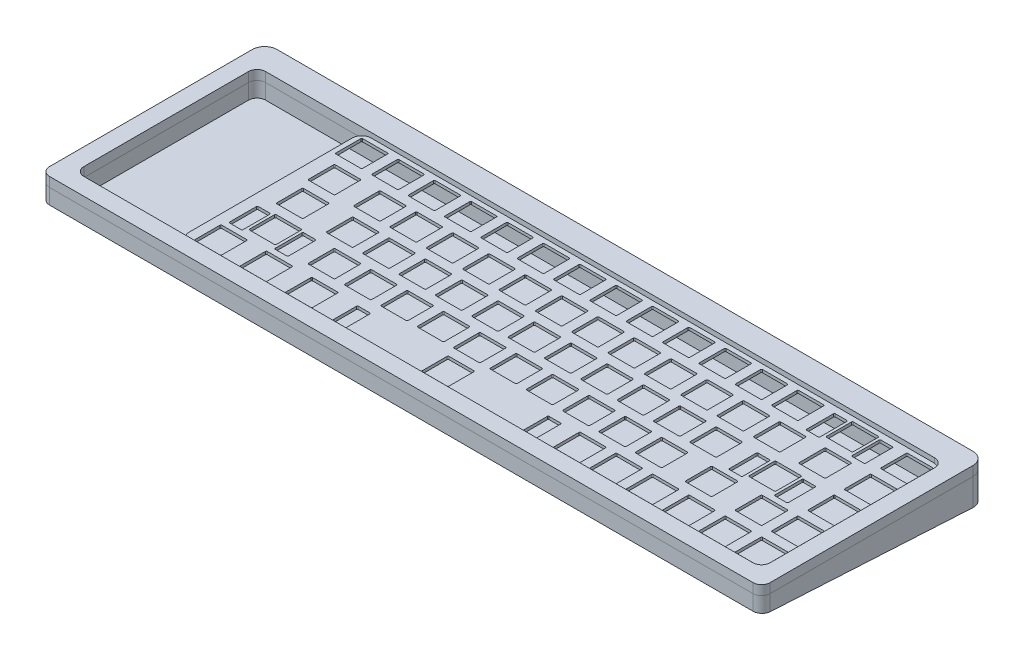
SolidWorks part; units mm, degrees
ref_plane "Front Plane" through (0, 0, 0) normal (0, 0, 1) x (1, 0, 0)
ref_plane "Top Plane" through (0, 0, 0) normal (0, 1, 0) x (1, 0, 0)
ref_plane "Right Plane" through (0, 0, 0) normal (1, 0, 0) x (0, 0, -1)
sketch "Sketch1" plane through (0, 0, 0) normal (0, 1, 0) x (1, 0, 0)
  line L0 (-179.825, 47.6224) -> (-179.825, 47.625)
  line L1 (-179.8217, 47.625) -> (179.825, 47.625)
  line L2 (-179.825, 47.6224) -> (-179.825, -47.625)
  line L3 (-179.825, -47.625) -> (179.825, -47.625)
  line L4 (179.825, 47.625) -> (179.825, -47.625)
  line L5 (-179.825, 47.625) -> (179.825, -47.625) construction
  line L6 (-179.825, -47.625) -> (179.825, 47.625) construction
  line L7 (-179.825, 47.625) -> (-179.8217, 47.625)
  circle A4 centre (157.075, 19.175) radius 1.1
  circle A5 centre (136.925, -16.775) radius 1.1
  circle A6 centre (-153.475, 33.725) radius 1.1
  circle A7 centre (17.925, 22.275) radius 1.1
  circle A8 centre (17.875, -35.075) radius 1.1
  circle A9 centre (-130.375, -35.725) radius 1.1
  point P0 (0, 0)
  dimension "D4" = 2.2
  dimension "D7" = 2.2
  dimension "D8" = 2.2
  dimension "D9" = 2.2
  dimension "D10" = 2.2
  dimension "D11" = 2.2
  dimension "D1" = 359.65
  dimension "D2" = 95.25
  dimension "D5" = 22.75
  dimension "D6" = 28.45
  dimension "D12" = 42.9
  dimension "D13" = 30.85
  dimension "D14" = 25.35
  dimension "D15" = 161.9
  dimension "D16" = 12.55
  dimension "D17" = 161.95
  dimension "D18" = 11.9
  dimension "D19" = 49.45
  dimension "D20" = 13.9
  dimension "D21" = 26.35
sketch "Sketch2" plane through (0, 0, 0) normal (0, 1, 0) x (1, 0, 0)
  line L0 (-188.825, 54.625) -> (-188.825, 60.625)
  line L1 (-188.825, 60.625) -> (-182.825, 60.625)
  line L4 (-179.825, 46.625) -> (-179.825, -46.625)
  line L5 (-178.825, -47.625) -> (178.825, -47.625)
  line L6 (179.825, 46.625) -> (179.825, -46.625)
  line L7 (-178.825, 47.625) -> (178.825, 47.625)
  line L8 (-179.825, 46.625) -> (-179.825, 47.625)
  line L9 (-182.825, 60.625) -> (188.825, 60.625)
  line L10 (-188.825, 54.625) -> (-188.825, -56.625)
  line L11 (-188.825, -56.625) -> (188.825, -56.625)
  line L12 (188.825, 60.625) -> (188.825, -56.625)
  line L13 (-179.825, 47.625) -> (-178.825, 47.625)
  line L14 (-179.825, -46.625) -> (-179.825, -47.625)
  line L15 (-179.825, -47.625) -> (-178.825, -47.625)
  line L16 (178.825, -47.625) -> (179.825, -47.625)
  line L17 (179.825, -47.625) -> (179.825, -46.625)
  line L18 (178.825, 47.625) -> (179.825, 47.625)
  line L19 (179.825, 47.625) -> (179.825, 46.625)
  circle A0 centre (157.075, 19.175) radius 1.1 construction
  circle A1 centre (136.925, -16.775) radius 1.1 construction
  circle A2 centre (17.875, -35.075) radius 1.1 construction
  circle A3 centre (17.925, 22.275) radius 1.1 construction
  circle A4 centre (-153.475, 33.725) radius 1.1 construction
  circle A5 centre (-130.375, -35.725) radius 1.1 construction
  circle A10 centre (157.075, 19.175) radius 1.1
  circle A11 centre (136.925, -16.775) radius 1.1
  circle A12 centre (17.875, -35.075) radius 1.1
  circle A13 centre (17.925, 22.275) radius 1.1
  circle A14 centre (-153.475, 33.725) radius 1.1
  circle A15 centre (-130.375, -35.725) radius 1.1
  point P30 (0, 0)
  dimension "D1" = 13
  dimension "D2" = 9
  dimension "D3" = 9
  dimension "D4" = 9
extrude "Boss-Extrude1" add sketch "Sketch2" along normal blind 13
sketch "Sketch4" plane through (0, 0, 0) normal (0, -1, 0) x (1, 0, 0)
  line L1 (-188.825, -60.625) -> (188.825, -60.625) construction
  line L3 (-188.825, 56.625) -> (188.825, 56.625) construction
  line L4 (-179.825, 47.625) -> (-179.825, -47.625)
  line L5 (179.825, 47.625) -> (-179.825, 47.625)
  line L6 (179.825, -47.625) -> (179.825, 47.625)
  line L7 (-179.825, -47.625) -> (179.825, -47.625)
  line L8 (-179.825, 47.625) -> (-179.825, -47.625)
  line L10 (179.825, -47.625) -> (179.825, 47.625)
  line L11 (-179.825, -47.625) -> (179.825, -47.625)
  line L12 (188.825, -60.625) -> (188.825, 56.625)
  line L13 (-188.825, -60.625) -> (188.825, -60.625)
  line L14 (-188.825, -60.625) -> (-188.825, 56.625)
  line L15 (-188.825, 56.625) -> (188.825, 56.625)
  line M10 (-179.825, -47.625) -> (-179.825, 47.625)
  line M12 (-179.825, 47.625) -> (179.825, 47.625)
  line M14 (179.825, 47.625) -> (179.825, -47.625)
  line M16 (179.825, -47.625) -> (-179.825, -47.625)
  line M17 (-188.825, 56.625) -> (-188.825, -60.625)
  line M19 (-188.825, -60.625) -> (188.825, -60.625)
  line M21 (188.825, -60.625) -> (188.825, 56.625)
  line M23 (188.825, 56.625) -> (-188.825, 56.625)
  dimension "D1" = 0
extrude "Boss-Extrude3" add sketch "Sketch4" along normal blind 10.5 contours M17 M19 M21 M23 M16 M10 M12 M14 | M16 M14 M12 M10 region at (0, 0, 0) region at (0, 0, -56.6707)
sketch "Sketch12" plane through (-188.825, 0, 0) normal (-1, 0, 0) x (0, 0, 1)
  line L0 (-60.625, 0) -> (56.625, 0) construction
  line L1 (-60.625, 13) -> (-60.625, -10.5) construction
  line L2 (56.625, 13) -> (56.625, -10.5) construction
  line L3 (56.625, -10.5) -> (-60.625, -10.5) construction
  line L4 (-60.625, -10.5) -> (-60.625, -6.5)
  line L5 (-60.625, -6.5) -> (56.625, 0)
  line L6 (56.625, 0) -> (56.625, -10.5)
  line L7 (56.625, -10.5) -> (-60.625, -10.5)
  dimension "D1" = 10.5
  dimension "D2" = 4
extrude "Cut-Extrude3" cut sketch "Sketch12" against normal blind 400
sketch "Sketch9" plane through (0, 0, 0) normal (0, 1, 0) x (1, 0, 0)
  line L0 (-121.9453, 45.1) -> (-108.9453, 45.1)
  line L1 (-121.9453, 31.1) -> (-108.9453, 31.1)
  line L2 (-122.4453, 44.6) -> (-122.4453, 31.6)
  line L3 (-108.4453, 44.6) -> (-108.4453, 31.6)
  line L4 (-102.8953, 45.1) -> (-89.8953, 45.1)
  line L5 (-102.8953, 31.1) -> (-89.8953, 31.1)
  line L6 (-103.3953, 44.6) -> (-103.3953, 31.6)
  line L7 (-89.3953, 44.6) -> (-89.3953, 31.6)
  line L8 (-83.8453, 45.1) -> (-70.8453, 45.1)
  line L9 (-83.8453, 31.1) -> (-70.8453, 31.1)
  line L10 (-84.3453, 44.6) -> (-84.3453, 31.6)
  line L11 (-70.3453, 44.6) -> (-70.3453, 31.6)
  line L12 (-64.7953, 45.1) -> (-51.7953, 45.1)
  line L13 (-64.7953, 31.1) -> (-51.7953, 31.1)
  line L14 (-65.2953, 44.6) -> (-65.2953, 31.6)
  line L15 (-51.2953, 44.6) -> (-51.2953, 31.6)
  line L16 (-45.7453, 45.1) -> (-32.7453, 45.1)
  line L17 (-45.7453, 31.1) -> (-32.7453, 31.1)
  line L18 (-46.2453, 44.6) -> (-46.2453, 31.6)
  line L19 (-32.2453, 44.6) -> (-32.2453, 31.6)
  line L20 (-26.6953, 45.1) -> (-13.6953, 45.1)
  line L21 (-26.6953, 31.1) -> (-13.6953, 31.1)
  line L22 (-27.1953, 44.6) -> (-27.1953, 31.6)
  line L23 (-13.1953, 44.6) -> (-13.1953, 31.6)
  line L24 (-7.6453, 45.1) -> (5.3547, 45.1)
  line L25 (-7.6453, 31.1) -> (5.3547, 31.1)
  line L26 (-8.1453, 44.6) -> (-8.1453, 31.6)
  line L27 (5.8547, 44.6) -> (5.8547, 31.6)
  line L28 (11.4047, 45.1) -> (24.4047, 45.1)
  line L29 (11.4047, 31.1) -> (24.4047, 31.1)
  line L30 (10.9047, 44.6) -> (10.9047, 31.6)
  line L31 (24.9047, 44.6) -> (24.9047, 31.6)
  line L32 (30.4547, 45.1) -> (43.4547, 45.1)
  line L33 (30.4547, 31.1) -> (43.4547, 31.1)
  line L34 (29.9547, 44.6) -> (29.9547, 31.6)
  line L35 (43.9547, 44.6) -> (43.9547, 31.6)
  line L36 (49.5047, 45.1) -> (62.5047, 45.1)
  line L37 (49.5047, 31.1) -> (62.5047, 31.1)
  line L38 (49.0047, 44.6) -> (49.0047, 31.6)
  line L39 (63.0047, 44.6) -> (63.0047, 31.6)
  line L40 (68.5547, 45.1) -> (81.5547, 45.1)
  line L41 (68.5547, 31.1) -> (81.5547, 31.1)
  line L42 (68.0547, 44.6) -> (68.0547, 31.6)
  line L43 (82.0547, 44.6) -> (82.0547, 31.6)
  line L44 (87.6047, 45.1) -> (100.6047, 45.1)
  line L45 (87.6047, 31.1) -> (100.6047, 31.1)
  line L46 (87.1047, 44.6) -> (87.1047, 31.6)
  line L47 (101.1047, 44.6) -> (101.1047, 31.6)
  line L48 (106.6547, 45.1) -> (119.6547, 45.1)
  line L49 (106.6547, 31.1) -> (119.6547, 31.1)
  line L50 (106.1547, 44.6) -> (106.1547, 31.6)
  line L51 (120.1547, 44.6) -> (120.1547, 31.6)
  line L52 (135.2297, 45.1) -> (148.2297, 45.1)
  line L53 (135.2297, 31.1) -> (148.2297, 31.1)
  line L54 (134.7297, 44.6) -> (134.7297, 31.6)
  line L55 (148.7297, 44.6) -> (148.7297, 31.6)
  line L56 (150.6677, 44.1) -> (156.6677, 44.1)
  line L57 (150.6677, 29.1) -> (156.6677, 29.1)
  line L58 (150.1677, 43.6) -> (150.1677, 29.6)
  line L59 (157.1677, 43.6) -> (157.1677, 29.6)
  line L60 (126.7917, 44.1) -> (132.7917, 44.1)
  line L61 (126.7917, 29.1) -> (132.7917, 29.1)
  line L62 (126.2917, 43.6) -> (126.2917, 29.6)
  line L63 (133.2917, 43.6) -> (133.2917, 29.6)
  line L64 (163.8047, 45.1) -> (176.8047, 45.1)
  line L65 (163.8047, 31.1) -> (176.8047, 31.1)
  line L66 (163.3047, 44.6) -> (163.3047, 31.6)
  line L67 (177.3047, 44.6) -> (177.3047, 31.6)
  line L68 (-117.1828, 26.05) -> (-104.1828, 26.05)
  line L69 (-117.1828, 12.05) -> (-104.1828, 12.05)
  line L70 (-117.6828, 25.55) -> (-117.6828, 12.55)
  line L71 (-103.6828, 25.55) -> (-103.6828, 12.55)
  line L72 (-93.3703, 26.05) -> (-80.3703, 26.05)
  line L73 (-93.3703, 12.05) -> (-80.3703, 12.05)
  line L74 (-93.8703, 25.55) -> (-93.8703, 12.55)
  line L75 (-79.8703, 25.55) -> (-79.8703, 12.55)
  line L76 (-74.3203, 26.05) -> (-61.3203, 26.05)
  line L77 (-74.3203, 12.05) -> (-61.3203, 12.05)
  line L78 (-74.8203, 25.55) -> (-74.8203, 12.55)
  line L79 (-60.8203, 25.55) -> (-60.8203, 12.55)
  line L80 (-55.2703, 26.05) -> (-42.2703, 26.05)
  line L81 (-55.2703, 12.05) -> (-42.2703, 12.05)
  line L82 (-55.7703, 25.55) -> (-55.7703, 12.55)
  line L83 (-41.7703, 25.55) -> (-41.7703, 12.55)
  line L84 (-36.2203, 26.05) -> (-23.2203, 26.05)
  line L85 (-36.2203, 12.05) -> (-23.2203, 12.05)
  line L86 (-36.7203, 25.55) -> (-36.7203, 12.55)
  line L87 (-22.7203, 25.55) -> (-22.7203, 12.55)
  line L88 (-17.1703, 26.05) -> (-4.1703, 26.05)
  line L89 (-17.1703, 12.05) -> (-4.1703, 12.05)
  line L90 (-17.6703, 25.55) -> (-17.6703, 12.55)
  line L91 (-3.6703, 25.55) -> (-3.6703, 12.55)
  line L92 (1.8797, 26.05) -> (14.8797, 26.05)
  line L93 (1.8797, 12.05) -> (14.8797, 12.05)
  line L94 (1.3797, 25.55) -> (1.3797, 12.55)
  line L95 (15.3797, 25.55) -> (15.3797, 12.55)
  line L96 (20.9297, 26.05) -> (33.9297, 26.05)
  line L97 (20.9297, 12.05) -> (33.9297, 12.05)
  line L98 (20.4297, 25.55) -> (20.4297, 12.55)
  line L99 (34.4297, 25.55) -> (34.4297, 12.55)
  line L100 (39.9797, 26.05) -> (52.9797, 26.05)
  line L101 (39.9797, 12.05) -> (52.9797, 12.05)
  line L102 (39.4797, 25.55) -> (39.4797, 12.55)
  line L103 (53.4797, 25.55) -> (53.4797, 12.55)
  line L104 (59.0297, 26.05) -> (72.0297, 26.05)
  line L105 (59.0297, 12.05) -> (72.0297, 12.05)
  line L106 (58.5297, 25.55) -> (58.5297, 12.55)
  line L107 (72.5297, 25.55) -> (72.5297, 12.55)
  line L108 (78.0797, 26.05) -> (91.0797, 26.05)
  line L109 (78.0797, 12.05) -> (91.0797, 12.05)
  line L110 (77.5797, 25.55) -> (77.5797, 12.55)
  line L111 (91.5797, 25.55) -> (91.5797, 12.55)
  line L112 (97.1297, 26.05) -> (110.1297, 26.05)
  line L113 (97.1297, 12.05) -> (110.1297, 12.05)
  line L114 (96.6297, 25.55) -> (96.6297, 12.55)
  line L115 (110.6297, 25.55) -> (110.6297, 12.55)
  line L116 (116.1797, 26.05) -> (129.1797, 26.05)
  line L117 (116.1797, 12.05) -> (129.1797, 12.05)
  line L118 (115.6797, 25.55) -> (115.6797, 12.55)
  line L119 (129.6797, 25.55) -> (129.6797, 12.55)
  line L120 (139.9922, 26.05) -> (152.9922, 26.05)
  line L121 (139.9922, 12.05) -> (152.9922, 12.05)
  line L122 (139.4922, 25.55) -> (139.4922, 12.55)
  line L123 (153.4922, 25.55) -> (153.4922, 12.55)
  line L124 (163.8047, 26.05) -> (176.8047, 26.05)
  line L125 (163.8047, 12.05) -> (176.8047, 12.05)
  line L126 (163.3047, 25.55) -> (163.3047, 12.55)
  line L127 (177.3047, 25.55) -> (177.3047, 12.55)
  line L128 (-114.8016, 7) -> (-101.8016, 7)
  line L129 (-114.8016, -7) -> (-101.8016, -7)
  line L130 (-115.3016, 6.5) -> (-115.3016, -6.5)
  line L131 (-101.3016, 6.5) -> (-101.3016, -6.5)
  line L132 (-88.6078, 7) -> (-75.6078, 7)
  line L133 (-88.6078, -7) -> (-75.6078, -7)
  line L134 (-89.1078, 6.5) -> (-89.1078, -6.5)
  line L135 (-75.1078, 6.5) -> (-75.1078, -6.5)
  line L136 (-69.5578, 7) -> (-56.5578, 7)
  line L137 (-69.5578, -7) -> (-56.5578, -7)
  line L138 (-70.0578, 6.5) -> (-70.0578, -6.5)
  line L139 (-56.0578, 6.5) -> (-56.0578, -6.5)
  line L140 (-50.5078, 7) -> (-37.5078, 7)
  line L141 (-50.5078, -7) -> (-37.5078, -7)
  line L142 (-51.0078, 6.5) -> (-51.0078, -6.5)
  line L143 (-37.0078, 6.5) -> (-37.0078, -6.5)
  line L144 (-31.4578, 7) -> (-18.4578, 7)
  line L145 (-31.4578, -7) -> (-18.4578, -7)
  line L146 (-31.9578, 6.5) -> (-31.9578, -6.5)
  line L147 (-17.9578, 6.5) -> (-17.9578, -6.5)
  line L148 (-12.4078, 7) -> (0.5922, 7)
  line L149 (-12.4078, -7) -> (0.5922, -7)
  line L150 (-12.9078, 6.5) -> (-12.9078, -6.5)
  line L151 (1.0922, 6.5) -> (1.0922, -6.5)
  line L152 (6.6422, 7) -> (19.6422, 7)
  line L153 (6.6422, -7) -> (19.6422, -7)
  line L154 (6.1422, 6.5) -> (6.1422, -6.5)
  line L155 (20.1422, 6.5) -> (20.1422, -6.5)
  line L156 (25.6922, 7) -> (38.6922, 7)
  line L157 (25.6922, -7) -> (38.6922, -7)
  line L158 (25.1922, 6.5) -> (25.1922, -6.5)
  line L159 (39.1922, 6.5) -> (39.1922, -6.5)
  line L160 (44.7422, 7) -> (57.7422, 7)
  line L161 (44.7422, -7) -> (57.7422, -7)
  line L162 (44.2422, 6.5) -> (44.2422, -6.5)
  line L163 (58.2422, 6.5) -> (58.2422, -6.5)
  line L164 (63.7922, 7) -> (76.7922, 7)
  line L165 (63.7922, -7) -> (76.7922, -7)
  line L166 (63.2922, 6.5) -> (63.2922, -6.5)
  line L167 (77.2922, 6.5) -> (77.2922, -6.5)
  line L168 (82.8422, 7) -> (95.8422, 7)
  line L169 (82.8422, -7) -> (95.8422, -7)
  line L170 (82.3422, 6.5) -> (82.3422, -6.5)
  line L171 (96.3422, 6.5) -> (96.3422, -6.5)
  line L172 (101.8922, 7) -> (114.8922, 7)
  line L173 (101.8922, -7) -> (114.8922, -7)
  line L174 (101.3922, 6.5) -> (101.3922, -6.5)
  line L175 (115.3922, 6.5) -> (115.3922, -6.5)
  line L176 (132.8484, 7) -> (145.8484, 7)
  line L177 (132.8484, -7) -> (145.8484, -7)
  line L178 (132.3484, 6.5) -> (132.3484, -6.5)
  line L179 (146.3484, 6.5) -> (146.3484, -6.5)
  line L180 (148.2864, 6) -> (154.2864, 6)
  line L181 (148.2864, -9) -> (154.2864, -9)
  line L182 (147.7864, 5.5) -> (147.7864, -8.5)
  line L183 (154.7864, 5.5) -> (154.7864, -8.5)
  line L184 (124.4104, 6) -> (130.4104, 6)
  line L185 (124.4104, -9) -> (130.4104, -9)
  line L186 (123.9104, 5.5) -> (123.9104, -8.5)
  line L187 (130.9104, 5.5) -> (130.9104, -8.5)
  line L188 (163.8047, 7) -> (176.8047, 7)
  line L189 (163.8047, -7) -> (176.8047, -7)
  line L190 (163.3047, 6.5) -> (163.3047, -6.5)
  line L191 (177.3047, 6.5) -> (177.3047, -6.5)
  line L192 (-110.0391, -12.05) -> (-97.0391, -12.05)
  line L193 (-110.0391, -26.05) -> (-97.0391, -26.05)
  line L194 (-110.5391, -12.55) -> (-110.5391, -25.55)
  line L195 (-96.5391, -12.55) -> (-96.5391, -25.55)
  line L196 (-94.6011, -13.05) -> (-88.6011, -13.05)
  line L197 (-94.6011, -28.05) -> (-88.6011, -28.05)
  line L198 (-95.1011, -13.55) -> (-95.1011, -27.55)
  line L199 (-88.1011, -13.55) -> (-88.1011, -27.55)
  line L200 (-118.4771, -13.05) -> (-112.4771, -13.05)
  line L201 (-118.4771, -28.05) -> (-112.4771, -28.05)
  line L202 (-118.9771, -13.55) -> (-118.9771, -27.55)
  line L203 (-111.9771, -13.55) -> (-111.9771, -27.55)
  line L204 (-79.0828, -12.05) -> (-66.0828, -12.05)
  line L205 (-79.0828, -26.05) -> (-66.0828, -26.05)
  line L206 (-79.5828, -12.55) -> (-79.5828, -25.55)
  line L207 (-65.5828, -12.55) -> (-65.5828, -25.55)
  line L208 (-60.0328, -12.05) -> (-47.0328, -12.05)
  line L209 (-60.0328, -26.05) -> (-47.0328, -26.05)
  line L210 (-60.5328, -12.55) -> (-60.5328, -25.55)
  line L211 (-46.5328, -12.55) -> (-46.5328, -25.55)
  line L212 (-40.9828, -12.05) -> (-27.9828, -12.05)
  line L213 (-40.9828, -26.05) -> (-27.9828, -26.05)
  line L214 (-41.4828, -12.55) -> (-41.4828, -25.55)
  line L215 (-27.4828, -12.55) -> (-27.4828, -25.55)
  line L216 (-21.9328, -12.05) -> (-8.9328, -12.05)
  line L217 (-21.9328, -26.05) -> (-8.9328, -26.05)
  line L218 (-22.4328, -12.55) -> (-22.4328, -25.55)
  line L219 (-8.4328, -12.55) -> (-8.4328, -25.55)
  line L220 (-2.8828, -12.05) -> (10.1172, -12.05)
  line L221 (-2.8828, -26.05) -> (10.1172, -26.05)
  line L222 (-3.3828, -12.55) -> (-3.3828, -25.55)
  line L223 (10.6172, -12.55) -> (10.6172, -25.55)
  line L224 (16.1672, -12.05) -> (29.1672, -12.05)
  line L225 (16.1672, -26.05) -> (29.1672, -26.05)
  line L226 (15.6672, -12.55) -> (15.6672, -25.55)
  line L227 (29.6672, -12.55) -> (29.6672, -25.55)
  line L228 (35.2172, -12.05) -> (48.2172, -12.05)
  line L229 (35.2172, -26.05) -> (48.2172, -26.05)
  line L230 (34.7172, -12.55) -> (34.7172, -25.55)
  line L231 (48.7172, -12.55) -> (48.7172, -25.55)
  line L232 (54.2672, -12.05) -> (67.2672, -12.05)
  line L233 (54.2672, -26.05) -> (67.2672, -26.05)
  line L234 (53.7672, -12.55) -> (53.7672, -25.55)
  line L235 (67.7672, -12.55) -> (67.7672, -25.55)
  line L236 (73.3172, -12.05) -> (86.3172, -12.05)
  line L237 (73.3172, -26.05) -> (86.3172, -26.05)
  line L238 (72.8172, -12.55) -> (72.8172, -25.55)
  line L239 (86.8172, -12.55) -> (86.8172, -25.55)
  line L240 (92.3672, -12.05) -> (105.3672, -12.05)
  line L241 (92.3672, -26.05) -> (105.3672, -26.05)
  line L242 (91.8672, -12.55) -> (91.8672, -25.55)
  line L243 (105.8672, -12.55) -> (105.8672, -25.55)
  line L244 (118.5609, -12.05) -> (131.5609, -12.05)
  line L245 (118.5609, -26.05) -> (131.5609, -26.05)
  line L246 (118.0609, -12.55) -> (118.0609, -25.55)
  line L247 (132.0609, -12.55) -> (132.0609, -25.55)
  line L248 (144.7547, -12.05) -> (157.7547, -12.05)
  line L249 (144.7547, -26.05) -> (157.7547, -26.05)
  line L250 (144.2547, -12.55) -> (144.2547, -25.55)
  line L251 (158.2547, -12.55) -> (158.2547, -25.55)
  line L252 (163.8047, -12.05) -> (176.8047, -12.05)
  line L253 (163.8047, -26.05) -> (176.8047, -26.05)
  line L254 (163.3047, -12.55) -> (163.3047, -25.55)
  line L255 (177.3047, -12.55) -> (177.3047, -25.55)
  line L256 (-119.5641, -31.1) -> (-106.5641, -31.1)
  line L257 (-119.5641, -45.1) -> (-106.5641, -45.1)
  line L258 (-120.0641, -31.6) -> (-120.0641, -44.6)
  line L259 (-106.0641, -31.6) -> (-106.0641, -44.6)
  line L260 (-95.7516, -31.1) -> (-82.7516, -31.1)
  line L261 (-95.7516, -45.1) -> (-82.7516, -45.1)
  line L262 (-96.2516, -31.6) -> (-96.2516, -44.6)
  line L263 (-82.2516, -31.6) -> (-82.2516, -44.6)
  line L264 (-71.9391, -31.1) -> (-58.9391, -31.1)
  line L265 (-71.9391, -45.1) -> (-58.9391, -45.1)
  line L266 (-72.4391, -31.6) -> (-72.4391, -44.6)
  line L267 (-58.4391, -31.6) -> (-58.4391, -44.6)
  line L268 (-0.5016, -31.1) -> (12.4984, -31.1)
  line L269 (-0.5016, -45.1) -> (12.4984, -45.1)
  line L270 (-1.0016, -31.6) -> (-1.0016, -44.6)
  line L271 (12.9984, -31.6) -> (12.9984, -44.6)
  line L272 (52.9984, -32.1) -> (58.9984, -32.1)
  line L273 (52.9984, -47.1) -> (58.9984, -47.1)
  line L274 (52.4984, -32.6) -> (52.4984, -46.6)
  line L275 (59.4984, -32.6) -> (59.4984, -46.6)
  line L276 (-47.0016, -32.1) -> (-41.0016, -32.1)
  line L277 (-47.0016, -47.1) -> (-41.0016, -47.1)
  line L278 (-47.5016, -32.6) -> (-47.5016, -46.6)
  line L279 (-40.5016, -32.6) -> (-40.5016, -46.6)
  line L280 (68.5547, -31.1) -> (81.5547, -31.1)
  line L281 (68.5547, -45.1) -> (81.5547, -45.1)
  line L282 (68.0547, -31.6) -> (68.0547, -44.6)
  line L283 (82.0547, -31.6) -> (82.0547, -44.6)
  line L284 (87.6047, -31.1) -> (100.6047, -31.1)
  line L285 (87.6047, -45.1) -> (100.6047, -45.1)
  line L286 (87.1047, -31.6) -> (87.1047, -44.6)
  line L287 (101.1047, -31.6) -> (101.1047, -44.6)
  line L288 (106.6547, -31.1) -> (119.6547, -31.1)
  line L289 (106.6547, -45.1) -> (119.6547, -45.1)
  line L290 (106.1547, -31.6) -> (106.1547, -44.6)
  line L291 (120.1547, -31.6) -> (120.1547, -44.6)
  line L292 (125.7047, -31.1) -> (138.7047, -31.1)
  line L293 (125.7047, -45.1) -> (138.7047, -45.1)
  line L294 (125.2047, -31.6) -> (125.2047, -44.6)
  line L295 (139.2047, -31.6) -> (139.2047, -44.6)
  line L296 (144.7547, -31.1) -> (157.7547, -31.1)
  line L297 (144.7547, -45.1) -> (157.7547, -45.1)
  line L298 (144.2547, -31.6) -> (144.2547, -44.6)
  line L299 (158.2547, -31.6) -> (158.2547, -44.6)
  line L300 (163.8047, -31.1) -> (176.8047, -31.1)
  line L301 (163.8047, -45.1) -> (176.8047, -45.1)
  line L302 (163.3047, -31.6) -> (163.3047, -44.6)
  line L303 (177.3047, -31.6) -> (177.3047, -44.6)
  line L304 (-119.9703, 47.625) -> (-103.2456, 47.625)
  line L305 (-119.9703, -47.625) -> (-100.699, -47.625)
  line L306 (-124.9703, 42.625) -> (-124.9703, -42.625)
  line L307 (179.8297, 42.625) -> (179.8297, 7.5)
  line L308 (-103.2456, 53.125) -> (-103.2456, 47.625)
  line L309 (-124.9703, 47.625) -> (-103.2456, 47.625)
  line L311 (-101.2456, 55.125) -> (-90.2456, 55.125)
  line L312 (-88.2456, 47.625) -> (-88.2456, 53.125)
  line L313 (-23.2456, 53.125) -> (-23.2456, 47.625)
  line L314 (-21.2456, 55.125) -> (-10.2456, 55.125)
  line L315 (-8.2456, 47.625) -> (-8.2456, 53.125)
  line L316 (56.7544, 53.125) -> (56.7544, 47.625)
  line L317 (58.7544, 55.125) -> (69.7544, 55.125)
  line L318 (71.7544, 47.625) -> (71.7544, 53.125)
  line L319 (136.7544, 53.125) -> (136.7544, 47.625)
  line L320 (138.7544, 55.125) -> (149.7544, 55.125)
  line L321 (151.7544, 47.625) -> (151.7544, 53.125)
  line L322 (-88.2456, 47.625) -> (-23.2456, 47.625)
  line L323 (-8.2456, 47.625) -> (56.7544, 47.625)
  line L324 (71.7544, 47.625) -> (136.7544, 47.625)
  line L325 (151.7544, 47.625) -> (174.8297, 47.625)
  line L326 (-20.699, -47.625) -> (-20.699, -52.625)
  line L327 (-5.699, -47.625) -> (-5.699, -52.625)
  line L329 (-100.699, -47.625) -> (-100.699, -52.625)
  line L330 (-98.699, -54.625) -> (-87.699, -54.625)
  line L331 (-85.699, -47.625) -> (-85.699, -52.625)
  line L332 (-18.699, -54.625) -> (-7.699, -54.625)
  line L333 (59.301, -47.625) -> (59.301, -52.625)
  line L334 (74.301, -47.625) -> (74.301, -52.625)
  line L335 (61.301, -54.625) -> (72.301, -54.625)
  line L336 (139.301, -47.625) -> (139.301, -52.625)
  line L337 (154.301, -47.625) -> (154.301, -52.625)
  line L338 (141.301, -54.625) -> (152.301, -54.625)
  line L339 (-85.699, -47.625) -> (-20.699, -47.625)
  line L340 (-5.699, -47.625) -> (59.301, -47.625)
  line L341 (74.301, -47.625) -> (139.301, -47.625)
  line L342 (154.301, -47.625) -> (174.8297, -47.625)
  line L343 (179.8297, -7.5) -> (179.8297, -42.625)
  line L348 (179.8297, 7.5) -> (179.8297, -7.5)
  arc A0 (-121.9453, 45.1) -> (-122.4453, 44.6) centre (-121.9453, 44.6) ccw
  arc A1 (-108.4453, 44.6) -> (-108.9453, 45.1) centre (-108.9453, 44.6) ccw
  arc A2 (-122.4453, 31.6) -> (-121.9453, 31.1) centre (-121.9453, 31.6) ccw
  arc A3 (-108.9453, 31.1) -> (-108.4453, 31.6) centre (-108.9453, 31.6) ccw
  arc A4 (-102.8953, 45.1) -> (-103.3953, 44.6) centre (-102.8953, 44.6) ccw
  arc A5 (-89.3953, 44.6) -> (-89.8953, 45.1) centre (-89.8953, 44.6) ccw
  arc A6 (-103.3953, 31.6) -> (-102.8953, 31.1) centre (-102.8953, 31.6) ccw
  arc A7 (-89.8953, 31.1) -> (-89.3953, 31.6) centre (-89.8953, 31.6) ccw
  arc A8 (-83.8453, 45.1) -> (-84.3453, 44.6) centre (-83.8453, 44.6) ccw
  arc A9 (-70.3453, 44.6) -> (-70.8453, 45.1) centre (-70.8453, 44.6) ccw
  arc A10 (-84.3453, 31.6) -> (-83.8453, 31.1) centre (-83.8453, 31.6) ccw
  arc A11 (-70.8453, 31.1) -> (-70.3453, 31.6) centre (-70.8453, 31.6) ccw
  arc A12 (-64.7953, 45.1) -> (-65.2953, 44.6) centre (-64.7953, 44.6) ccw
  arc A13 (-51.2953, 44.6) -> (-51.7953, 45.1) centre (-51.7953, 44.6) ccw
  arc A14 (-65.2953, 31.6) -> (-64.7953, 31.1) centre (-64.7953, 31.6) ccw
  arc A15 (-51.7953, 31.1) -> (-51.2953, 31.6) centre (-51.7953, 31.6) ccw
  arc A16 (-45.7453, 45.1) -> (-46.2453, 44.6) centre (-45.7453, 44.6) ccw
  arc A17 (-32.2453, 44.6) -> (-32.7453, 45.1) centre (-32.7453, 44.6) ccw
  arc A18 (-46.2453, 31.6) -> (-45.7453, 31.1) centre (-45.7453, 31.6) ccw
  arc A19 (-32.7453, 31.1) -> (-32.2453, 31.6) centre (-32.7453, 31.6) ccw
  arc A20 (-26.6953, 45.1) -> (-27.1953, 44.6) centre (-26.6953, 44.6) ccw
  arc A21 (-13.1953, 44.6) -> (-13.6953, 45.1) centre (-13.6953, 44.6) ccw
  arc A22 (-27.1953, 31.6) -> (-26.6953, 31.1) centre (-26.6953, 31.6) ccw
  arc A23 (-13.6953, 31.1) -> (-13.1953, 31.6) centre (-13.6953, 31.6) ccw
  arc A24 (-7.6453, 45.1) -> (-8.1453, 44.6) centre (-7.6453, 44.6) ccw
  arc A25 (5.8547, 44.6) -> (5.3547, 45.1) centre (5.3547, 44.6) ccw
  arc A26 (-8.1453, 31.6) -> (-7.6453, 31.1) centre (-7.6453, 31.6) ccw
  arc A27 (5.3547, 31.1) -> (5.8547, 31.6) centre (5.3547, 31.6) ccw
  arc A28 (11.4047, 45.1) -> (10.9047, 44.6) centre (11.4047, 44.6) ccw
  arc A29 (24.9047, 44.6) -> (24.4047, 45.1) centre (24.4047, 44.6) ccw
  arc A30 (10.9047, 31.6) -> (11.4047, 31.1) centre (11.4047, 31.6) ccw
  arc A31 (24.4047, 31.1) -> (24.9047, 31.6) centre (24.4047, 31.6) ccw
  arc A32 (30.4547, 45.1) -> (29.9547, 44.6) centre (30.4547, 44.6) ccw
  arc A33 (43.9547, 44.6) -> (43.4547, 45.1) centre (43.4547, 44.6) ccw
  arc A34 (29.9547, 31.6) -> (30.4547, 31.1) centre (30.4547, 31.6) ccw
  arc A35 (43.4547, 31.1) -> (43.9547, 31.6) centre (43.4547, 31.6) ccw
  arc A36 (49.5047, 45.1) -> (49.0047, 44.6) centre (49.5047, 44.6) ccw
  arc A37 (63.0047, 44.6) -> (62.5047, 45.1) centre (62.5047, 44.6) ccw
  arc A38 (49.0047, 31.6) -> (49.5047, 31.1) centre (49.5047, 31.6) ccw
  arc A39 (62.5047, 31.1) -> (63.0047, 31.6) centre (62.5047, 31.6) ccw
  arc A40 (68.5547, 45.1) -> (68.0547, 44.6) centre (68.5547, 44.6) ccw
  arc A41 (82.0547, 44.6) -> (81.5547, 45.1) centre (81.5547, 44.6) ccw
  arc A42 (68.0547, 31.6) -> (68.5547, 31.1) centre (68.5547, 31.6) ccw
  arc A43 (81.5547, 31.1) -> (82.0547, 31.6) centre (81.5547, 31.6) ccw
  arc A44 (87.6047, 45.1) -> (87.1047, 44.6) centre (87.6047, 44.6) ccw
  arc A45 (101.1047, 44.6) -> (100.6047, 45.1) centre (100.6047, 44.6) ccw
  arc A46 (87.1047, 31.6) -> (87.6047, 31.1) centre (87.6047, 31.6) ccw
  arc A47 (100.6047, 31.1) -> (101.1047, 31.6) centre (100.6047, 31.6) ccw
  arc A48 (106.6547, 45.1) -> (106.1547, 44.6) centre (106.6547, 44.6) ccw
  arc A49 (120.1547, 44.6) -> (119.6547, 45.1) centre (119.6547, 44.6) ccw
  arc A50 (106.1547, 31.6) -> (106.6547, 31.1) centre (106.6547, 31.6) ccw
  arc A51 (119.6547, 31.1) -> (120.1547, 31.6) centre (119.6547, 31.6) ccw
  arc A52 (135.2297, 45.1) -> (134.7297, 44.6) centre (135.2297, 44.6) ccw
  arc A53 (148.7297, 44.6) -> (148.2297, 45.1) centre (148.2297, 44.6) ccw
  arc A54 (134.7297, 31.6) -> (135.2297, 31.1) centre (135.2297, 31.6) ccw
  arc A55 (148.2297, 31.1) -> (148.7297, 31.6) centre (148.2297, 31.6) ccw
  arc A56 (150.6677, 44.1) -> (150.1677, 43.6) centre (150.6677, 43.6) ccw
  arc A57 (157.1677, 43.6) -> (156.6677, 44.1) centre (156.6677, 43.6) ccw
  arc A58 (150.1677, 29.6) -> (150.6677, 29.1) centre (150.6677, 29.6) ccw
  arc A59 (156.6677, 29.1) -> (157.1677, 29.6) centre (156.6677, 29.6) ccw
  arc A60 (126.7917, 44.1) -> (126.2917, 43.6) centre (126.7917, 43.6) ccw
  arc A61 (133.2917, 43.6) -> (132.7917, 44.1) centre (132.7917, 43.6) ccw
  arc A62 (126.2917, 29.6) -> (126.7917, 29.1) centre (126.7917, 29.6) ccw
  arc A63 (132.7917, 29.1) -> (133.2917, 29.6) centre (132.7917, 29.6) ccw
  arc A64 (163.8047, 45.1) -> (163.3047, 44.6) centre (163.8047, 44.6) ccw
  arc A65 (177.3047, 44.6) -> (176.8047, 45.1) centre (176.8047, 44.6) ccw
  arc A66 (163.3047, 31.6) -> (163.8047, 31.1) centre (163.8047, 31.6) ccw
  arc A67 (176.8047, 31.1) -> (177.3047, 31.6) centre (176.8047, 31.6) ccw
  arc A68 (-117.1828, 26.05) -> (-117.6828, 25.55) centre (-117.1828, 25.55) ccw
  arc A69 (-103.6828, 25.55) -> (-104.1828, 26.05) centre (-104.1828, 25.55) ccw
  arc A70 (-117.6828, 12.55) -> (-117.1828, 12.05) centre (-117.1828, 12.55) ccw
  arc A71 (-104.1828, 12.05) -> (-103.6828, 12.55) centre (-104.1828, 12.55) ccw
  arc A72 (-93.3703, 26.05) -> (-93.8703, 25.55) centre (-93.3703, 25.55) ccw
  arc A73 (-79.8703, 25.55) -> (-80.3703, 26.05) centre (-80.3703, 25.55) ccw
  arc A74 (-93.8703, 12.55) -> (-93.3703, 12.05) centre (-93.3703, 12.55) ccw
  arc A75 (-80.3703, 12.05) -> (-79.8703, 12.55) centre (-80.3703, 12.55) ccw
  arc A76 (-74.3203, 26.05) -> (-74.8203, 25.55) centre (-74.3203, 25.55) ccw
  arc A77 (-60.8203, 25.55) -> (-61.3203, 26.05) centre (-61.3203, 25.55) ccw
  arc A78 (-74.8203, 12.55) -> (-74.3203, 12.05) centre (-74.3203, 12.55) ccw
  arc A79 (-61.3203, 12.05) -> (-60.8203, 12.55) centre (-61.3203, 12.55) ccw
  arc A80 (-55.2703, 26.05) -> (-55.7703, 25.55) centre (-55.2703, 25.55) ccw
  arc A81 (-41.7703, 25.55) -> (-42.2703, 26.05) centre (-42.2703, 25.55) ccw
  arc A82 (-55.7703, 12.55) -> (-55.2703, 12.05) centre (-55.2703, 12.55) ccw
  arc A83 (-42.2703, 12.05) -> (-41.7703, 12.55) centre (-42.2703, 12.55) ccw
  arc A84 (-36.2203, 26.05) -> (-36.7203, 25.55) centre (-36.2203, 25.55) ccw
  arc A85 (-22.7203, 25.55) -> (-23.2203, 26.05) centre (-23.2203, 25.55) ccw
  arc A86 (-36.7203, 12.55) -> (-36.2203, 12.05) centre (-36.2203, 12.55) ccw
  arc A87 (-23.2203, 12.05) -> (-22.7203, 12.55) centre (-23.2203, 12.55) ccw
  arc A88 (-17.1703, 26.05) -> (-17.6703, 25.55) centre (-17.1703, 25.55) ccw
  arc A89 (-3.6703, 25.55) -> (-4.1703, 26.05) centre (-4.1703, 25.55) ccw
  arc A90 (-17.6703, 12.55) -> (-17.1703, 12.05) centre (-17.1703, 12.55) ccw
  arc A91 (-4.1703, 12.05) -> (-3.6703, 12.55) centre (-4.1703, 12.55) ccw
  arc A92 (1.8797, 26.05) -> (1.3797, 25.55) centre (1.8797, 25.55) ccw
  arc A93 (15.3797, 25.55) -> (14.8797, 26.05) centre (14.8797, 25.55) ccw
  arc A94 (1.3797, 12.55) -> (1.8797, 12.05) centre (1.8797, 12.55) ccw
  arc A95 (14.8797, 12.05) -> (15.3797, 12.55) centre (14.8797, 12.55) ccw
  arc A96 (20.9297, 26.05) -> (20.4297, 25.55) centre (20.9297, 25.55) ccw
  arc A97 (34.4297, 25.55) -> (33.9297, 26.05) centre (33.9297, 25.55) ccw
  arc A98 (20.4297, 12.55) -> (20.9297, 12.05) centre (20.9297, 12.55) ccw
  arc A99 (33.9297, 12.05) -> (34.4297, 12.55) centre (33.9297, 12.55) ccw
  arc A100 (39.9797, 26.05) -> (39.4797, 25.55) centre (39.9797, 25.55) ccw
  arc A101 (53.4797, 25.55) -> (52.9797, 26.05) centre (52.9797, 25.55) ccw
  arc A102 (39.4797, 12.55) -> (39.9797, 12.05) centre (39.9797, 12.55) ccw
  arc A103 (52.9797, 12.05) -> (53.4797, 12.55) centre (52.9797, 12.55) ccw
  arc A104 (59.0297, 26.05) -> (58.5297, 25.55) centre (59.0297, 25.55) ccw
  arc A105 (72.5297, 25.55) -> (72.0297, 26.05) centre (72.0297, 25.55) ccw
  arc A106 (58.5297, 12.55) -> (59.0297, 12.05) centre (59.0297, 12.55) ccw
  arc A107 (72.0297, 12.05) -> (72.5297, 12.55) centre (72.0297, 12.55) ccw
  arc A108 (78.0797, 26.05) -> (77.5797, 25.55) centre (78.0797, 25.55) ccw
  arc A109 (91.5797, 25.55) -> (91.0797, 26.05) centre (91.0797, 25.55) ccw
  arc A110 (77.5797, 12.55) -> (78.0797, 12.05) centre (78.0797, 12.55) ccw
  arc A111 (91.0797, 12.05) -> (91.5797, 12.55) centre (91.0797, 12.55) ccw
  arc A112 (97.1297, 26.05) -> (96.6297, 25.55) centre (97.1297, 25.55) ccw
  arc A113 (110.6297, 25.55) -> (110.1297, 26.05) centre (110.1297, 25.55) ccw
  arc A114 (96.6297, 12.55) -> (97.1297, 12.05) centre (97.1297, 12.55) ccw
  arc A115 (110.1297, 12.05) -> (110.6297, 12.55) centre (110.1297, 12.55) ccw
  arc A116 (116.1797, 26.05) -> (115.6797, 25.55) centre (116.1797, 25.55) ccw
  arc A117 (129.6797, 25.55) -> (129.1797, 26.05) centre (129.1797, 25.55) ccw
  arc A118 (115.6797, 12.55) -> (116.1797, 12.05) centre (116.1797, 12.55) ccw
  arc A119 (129.1797, 12.05) -> (129.6797, 12.55) centre (129.1797, 12.55) ccw
  arc A120 (139.9922, 26.05) -> (139.4922, 25.55) centre (139.9922, 25.55) ccw
  arc A121 (153.4922, 25.55) -> (152.9922, 26.05) centre (152.9922, 25.55) ccw
  arc A122 (139.4922, 12.55) -> (139.9922, 12.05) centre (139.9922, 12.55) ccw
  arc A123 (152.9922, 12.05) -> (153.4922, 12.55) centre (152.9922, 12.55) ccw
  arc A124 (163.8047, 26.05) -> (163.3047, 25.55) centre (163.8047, 25.55) ccw
  arc A125 (177.3047, 25.55) -> (176.8047, 26.05) centre (176.8047, 25.55) ccw
  arc A126 (163.3047, 12.55) -> (163.8047, 12.05) centre (163.8047, 12.55) ccw
  arc A127 (176.8047, 12.05) -> (177.3047, 12.55) centre (176.8047, 12.55) ccw
  arc A128 (-114.8016, 7) -> (-115.3016, 6.5) centre (-114.8016, 6.5) ccw
  arc A129 (-101.3016, 6.5) -> (-101.8016, 7) centre (-101.8016, 6.5) ccw
  arc A130 (-115.3016, -6.5) -> (-114.8016, -7) centre (-114.8016, -6.5) ccw
  arc A131 (-101.8016, -7) -> (-101.3016, -6.5) centre (-101.8016, -6.5) ccw
  arc A132 (-88.6078, 7) -> (-89.1078, 6.5) centre (-88.6078, 6.5) ccw
  arc A133 (-75.1078, 6.5) -> (-75.6078, 7) centre (-75.6078, 6.5) ccw
  arc A134 (-89.1078, -6.5) -> (-88.6078, -7) centre (-88.6078, -6.5) ccw
  arc A135 (-75.6078, -7) -> (-75.1078, -6.5) centre (-75.6078, -6.5) ccw
  arc A136 (-69.5578, 7) -> (-70.0578, 6.5) centre (-69.5578, 6.5) ccw
  arc A137 (-56.0578, 6.5) -> (-56.5578, 7) centre (-56.5578, 6.5) ccw
  arc A138 (-70.0578, -6.5) -> (-69.5578, -7) centre (-69.5578, -6.5) ccw
  arc A139 (-56.5578, -7) -> (-56.0578, -6.5) centre (-56.5578, -6.5) ccw
  arc A140 (-50.5078, 7) -> (-51.0078, 6.5) centre (-50.5078, 6.5) ccw
  arc A141 (-37.0078, 6.5) -> (-37.5078, 7) centre (-37.5078, 6.5) ccw
  arc A142 (-51.0078, -6.5) -> (-50.5078, -7) centre (-50.5078, -6.5) ccw
  arc A143 (-37.5078, -7) -> (-37.0078, -6.5) centre (-37.5078, -6.5) ccw
  arc A144 (-31.4578, 7) -> (-31.9578, 6.5) centre (-31.4578, 6.5) ccw
  arc A145 (-17.9578, 6.5) -> (-18.4578, 7) centre (-18.4578, 6.5) ccw
  arc A146 (-31.9578, -6.5) -> (-31.4578, -7) centre (-31.4578, -6.5) ccw
  arc A147 (-18.4578, -7) -> (-17.9578, -6.5) centre (-18.4578, -6.5) ccw
  arc A148 (-12.4078, 7) -> (-12.9078, 6.5) centre (-12.4078, 6.5) ccw
  arc A149 (1.0922, 6.5) -> (0.5922, 7) centre (0.5922, 6.5) ccw
  arc A150 (-12.9078, -6.5) -> (-12.4078, -7) centre (-12.4078, -6.5) ccw
  arc A151 (0.5922, -7) -> (1.0922, -6.5) centre (0.5922, -6.5) ccw
  arc A152 (6.6422, 7) -> (6.1422, 6.5) centre (6.6422, 6.5) ccw
  arc A153 (20.1422, 6.5) -> (19.6422, 7) centre (19.6422, 6.5) ccw
  arc A154 (6.1422, -6.5) -> (6.6422, -7) centre (6.6422, -6.5) ccw
  arc A155 (19.6422, -7) -> (20.1422, -6.5) centre (19.6422, -6.5) ccw
  arc A156 (25.6922, 7) -> (25.1922, 6.5) centre (25.6922, 6.5) ccw
  arc A157 (39.1922, 6.5) -> (38.6922, 7) centre (38.6922, 6.5) ccw
  arc A158 (25.1922, -6.5) -> (25.6922, -7) centre (25.6922, -6.5) ccw
  arc A159 (38.6922, -7) -> (39.1922, -6.5) centre (38.6922, -6.5) ccw
  arc A160 (44.7422, 7) -> (44.2422, 6.5) centre (44.7422, 6.5) ccw
  arc A161 (58.2422, 6.5) -> (57.7422, 7) centre (57.7422, 6.5) ccw
  arc A162 (44.2422, -6.5) -> (44.7422, -7) centre (44.7422, -6.5) ccw
  arc A163 (57.7422, -7) -> (58.2422, -6.5) centre (57.7422, -6.5) ccw
  arc A164 (63.7922, 7) -> (63.2922, 6.5) centre (63.7922, 6.5) ccw
  arc A165 (77.2922, 6.5) -> (76.7922, 7) centre (76.7922, 6.5) ccw
  arc A166 (63.2922, -6.5) -> (63.7922, -7) centre (63.7922, -6.5) ccw
  arc A167 (76.7922, -7) -> (77.2922, -6.5) centre (76.7922, -6.5) ccw
  arc A168 (82.8422, 7) -> (82.3422, 6.5) centre (82.8422, 6.5) ccw
  arc A169 (96.3422, 6.5) -> (95.8422, 7) centre (95.8422, 6.5) ccw
  arc A170 (82.3422, -6.5) -> (82.8422, -7) centre (82.8422, -6.5) ccw
  arc A171 (95.8422, -7) -> (96.3422, -6.5) centre (95.8422, -6.5) ccw
  arc A172 (101.8922, 7) -> (101.3922, 6.5) centre (101.8922, 6.5) ccw
  arc A173 (115.3922, 6.5) -> (114.8922, 7) centre (114.8922, 6.5) ccw
  arc A174 (101.3922, -6.5) -> (101.8922, -7) centre (101.8922, -6.5) ccw
  arc A175 (114.8922, -7) -> (115.3922, -6.5) centre (114.8922, -6.5) ccw
  arc A176 (132.8484, 7) -> (132.3484, 6.5) centre (132.8484, 6.5) ccw
  arc A177 (146.3484, 6.5) -> (145.8484, 7) centre (145.8484, 6.5) ccw
  arc A178 (132.3484, -6.5) -> (132.8484, -7) centre (132.8484, -6.5) ccw
  arc A179 (145.8484, -7) -> (146.3484, -6.5) centre (145.8484, -6.5) ccw
  arc A180 (148.2864, 6) -> (147.7864, 5.5) centre (148.2864, 5.5) ccw
  arc A181 (154.7864, 5.5) -> (154.2864, 6) centre (154.2864, 5.5) ccw
  arc A182 (147.7864, -8.5) -> (148.2864, -9) centre (148.2864, -8.5) ccw
  arc A183 (154.2864, -9) -> (154.7864, -8.5) centre (154.2864, -8.5) ccw
  arc A184 (124.4104, 6) -> (123.9104, 5.5) centre (124.4104, 5.5) ccw
  arc A185 (130.9104, 5.5) -> (130.4104, 6) centre (130.4104, 5.5) ccw
  arc A186 (123.9104, -8.5) -> (124.4104, -9) centre (124.4104, -8.5) ccw
  arc A187 (130.4104, -9) -> (130.9104, -8.5) centre (130.4104, -8.5) ccw
  arc A188 (163.8047, 7) -> (163.3047, 6.5) centre (163.8047, 6.5) ccw
  arc A189 (177.3047, 6.5) -> (176.8047, 7) centre (176.8047, 6.5) ccw
  arc A190 (163.3047, -6.5) -> (163.8047, -7) centre (163.8047, -6.5) ccw
  arc A191 (176.8047, -7) -> (177.3047, -6.5) centre (176.8047, -6.5) ccw
  arc A192 (-110.0391, -12.05) -> (-110.5391, -12.55) centre (-110.0391, -12.55) ccw
  arc A193 (-96.5391, -12.55) -> (-97.0391, -12.05) centre (-97.0391, -12.55) ccw
  arc A194 (-110.5391, -25.55) -> (-110.0391, -26.05) centre (-110.0391, -25.55) ccw
  arc A195 (-97.0391, -26.05) -> (-96.5391, -25.55) centre (-97.0391, -25.55) ccw
  arc A196 (-94.6011, -13.05) -> (-95.1011, -13.55) centre (-94.6011, -13.55) ccw
  arc A197 (-88.1011, -13.55) -> (-88.6011, -13.05) centre (-88.6011, -13.55) ccw
  arc A198 (-95.1011, -27.55) -> (-94.6011, -28.05) centre (-94.6011, -27.55) ccw
  arc A199 (-88.6011, -28.05) -> (-88.1011, -27.55) centre (-88.6011, -27.55) ccw
  arc A200 (-118.4771, -13.05) -> (-118.9771, -13.55) centre (-118.4771, -13.55) ccw
  arc A201 (-111.9771, -13.55) -> (-112.4771, -13.05) centre (-112.4771, -13.55) ccw
  arc A202 (-118.9771, -27.55) -> (-118.4771, -28.05) centre (-118.4771, -27.55) ccw
  arc A203 (-112.4771, -28.05) -> (-111.9771, -27.55) centre (-112.4771, -27.55) ccw
  arc A204 (-79.0828, -12.05) -> (-79.5828, -12.55) centre (-79.0828, -12.55) ccw
  arc A205 (-65.5828, -12.55) -> (-66.0828, -12.05) centre (-66.0828, -12.55) ccw
  arc A206 (-79.5828, -25.55) -> (-79.0828, -26.05) centre (-79.0828, -25.55) ccw
  arc A207 (-66.0828, -26.05) -> (-65.5828, -25.55) centre (-66.0828, -25.55) ccw
  arc A208 (-60.0328, -12.05) -> (-60.5328, -12.55) centre (-60.0328, -12.55) ccw
  arc A209 (-46.5328, -12.55) -> (-47.0328, -12.05) centre (-47.0328, -12.55) ccw
  arc A210 (-60.5328, -25.55) -> (-60.0328, -26.05) centre (-60.0328, -25.55) ccw
  arc A211 (-47.0328, -26.05) -> (-46.5328, -25.55) centre (-47.0328, -25.55) ccw
  arc A212 (-40.9828, -12.05) -> (-41.4828, -12.55) centre (-40.9828, -12.55) ccw
  arc A213 (-27.4828, -12.55) -> (-27.9828, -12.05) centre (-27.9828, -12.55) ccw
  arc A214 (-41.4828, -25.55) -> (-40.9828, -26.05) centre (-40.9828, -25.55) ccw
  arc A215 (-27.9828, -26.05) -> (-27.4828, -25.55) centre (-27.9828, -25.55) ccw
  arc A216 (-21.9328, -12.05) -> (-22.4328, -12.55) centre (-21.9328, -12.55) ccw
  arc A217 (-8.4328, -12.55) -> (-8.9328, -12.05) centre (-8.9328, -12.55) ccw
  arc A218 (-22.4328, -25.55) -> (-21.9328, -26.05) centre (-21.9328, -25.55) ccw
  arc A219 (-8.9328, -26.05) -> (-8.4328, -25.55) centre (-8.9328, -25.55) ccw
  arc A220 (-2.8828, -12.05) -> (-3.3828, -12.55) centre (-2.8828, -12.55) ccw
  arc A221 (10.6172, -12.55) -> (10.1172, -12.05) centre (10.1172, -12.55) ccw
  arc A222 (-3.3828, -25.55) -> (-2.8828, -26.05) centre (-2.8828, -25.55) ccw
  arc A223 (10.1172, -26.05) -> (10.6172, -25.55) centre (10.1172, -25.55) ccw
  arc A224 (16.1672, -12.05) -> (15.6672, -12.55) centre (16.1672, -12.55) ccw
  arc A225 (29.6672, -12.55) -> (29.1672, -12.05) centre (29.1672, -12.55) ccw
  arc A226 (15.6672, -25.55) -> (16.1672, -26.05) centre (16.1672, -25.55) ccw
  arc A227 (29.1672, -26.05) -> (29.6672, -25.55) centre (29.1672, -25.55) ccw
  arc A228 (35.2172, -12.05) -> (34.7172, -12.55) centre (35.2172, -12.55) ccw
  arc A229 (48.7172, -12.55) -> (48.2172, -12.05) centre (48.2172, -12.55) ccw
  arc A230 (34.7172, -25.55) -> (35.2172, -26.05) centre (35.2172, -25.55) ccw
  arc A231 (48.2172, -26.05) -> (48.7172, -25.55) centre (48.2172, -25.55) ccw
  arc A232 (54.2672, -12.05) -> (53.7672, -12.55) centre (54.2672, -12.55) ccw
  arc A233 (67.7672, -12.55) -> (67.2672, -12.05) centre (67.2672, -12.55) ccw
  arc A234 (53.7672, -25.55) -> (54.2672, -26.05) centre (54.2672, -25.55) ccw
  arc A235 (67.2672, -26.05) -> (67.7672, -25.55) centre (67.2672, -25.55) ccw
  arc A236 (73.3172, -12.05) -> (72.8172, -12.55) centre (73.3172, -12.55) ccw
  arc A237 (86.8172, -12.55) -> (86.3172, -12.05) centre (86.3172, -12.55) ccw
  arc A238 (72.8172, -25.55) -> (73.3172, -26.05) centre (73.3172, -25.55) ccw
  arc A239 (86.3172, -26.05) -> (86.8172, -25.55) centre (86.3172, -25.55) ccw
  arc A240 (92.3672, -12.05) -> (91.8672, -12.55) centre (92.3672, -12.55) ccw
  arc A241 (105.8672, -12.55) -> (105.3672, -12.05) centre (105.3672, -12.55) ccw
  arc A242 (91.8672, -25.55) -> (92.3672, -26.05) centre (92.3672, -25.55) ccw
  arc A243 (105.3672, -26.05) -> (105.8672, -25.55) centre (105.3672, -25.55) ccw
  arc A244 (118.5609, -12.05) -> (118.0609, -12.55) centre (118.5609, -12.55) ccw
  arc A245 (132.0609, -12.55) -> (131.5609, -12.05) centre (131.5609, -12.55) ccw
  arc A246 (118.0609, -25.55) -> (118.5609, -26.05) centre (118.5609, -25.55) ccw
  arc A247 (131.5609, -26.05) -> (132.0609, -25.55) centre (131.5609, -25.55) ccw
  arc A248 (144.7547, -12.05) -> (144.2547, -12.55) centre (144.7547, -12.55) ccw
  arc A249 (158.2547, -12.55) -> (157.7547, -12.05) centre (157.7547, -12.55) ccw
  arc A250 (144.2547, -25.55) -> (144.7547, -26.05) centre (144.7547, -25.55) ccw
  arc A251 (157.7547, -26.05) -> (158.2547, -25.55) centre (157.7547, -25.55) ccw
  arc A252 (163.8047, -12.05) -> (163.3047, -12.55) centre (163.8047, -12.55) ccw
  arc A253 (177.3047, -12.55) -> (176.8047, -12.05) centre (176.8047, -12.55) ccw
  arc A254 (163.3047, -25.55) -> (163.8047, -26.05) centre (163.8047, -25.55) ccw
  arc A255 (176.8047, -26.05) -> (177.3047, -25.55) centre (176.8047, -25.55) ccw
  arc A256 (-119.5641, -31.1) -> (-120.0641, -31.6) centre (-119.5641, -31.6) ccw
  arc A257 (-106.0641, -31.6) -> (-106.5641, -31.1) centre (-106.5641, -31.6) ccw
  arc A258 (-120.0641, -44.6) -> (-119.5641, -45.1) centre (-119.5641, -44.6) ccw
  arc A259 (-106.5641, -45.1) -> (-106.0641, -44.6) centre (-106.5641, -44.6) ccw
  arc A260 (-95.7516, -31.1) -> (-96.2516, -31.6) centre (-95.7516, -31.6) ccw
  arc A261 (-82.2516, -31.6) -> (-82.7516, -31.1) centre (-82.7516, -31.6) ccw
  arc A262 (-96.2516, -44.6) -> (-95.7516, -45.1) centre (-95.7516, -44.6) ccw
  arc A263 (-82.7516, -45.1) -> (-82.2516, -44.6) centre (-82.7516, -44.6) ccw
  arc A264 (-71.9391, -31.1) -> (-72.4391, -31.6) centre (-71.9391, -31.6) ccw
  arc A265 (-58.4391, -31.6) -> (-58.9391, -31.1) centre (-58.9391, -31.6) ccw
  arc A266 (-72.4391, -44.6) -> (-71.9391, -45.1) centre (-71.9391, -44.6) ccw
  arc A267 (-58.9391, -45.1) -> (-58.4391, -44.6) centre (-58.9391, -44.6) ccw
  arc A268 (-0.5016, -31.1) -> (-1.0016, -31.6) centre (-0.5016, -31.6) ccw
  arc A269 (12.9984, -31.6) -> (12.4984, -31.1) centre (12.4984, -31.6) ccw
  arc A270 (-1.0016, -44.6) -> (-0.5016, -45.1) centre (-0.5016, -44.6) ccw
  arc A271 (12.4984, -45.1) -> (12.9984, -44.6) centre (12.4984, -44.6) ccw
  arc A272 (52.9984, -32.1) -> (52.4984, -32.6) centre (52.9984, -32.6) ccw
  arc A273 (59.4984, -32.6) -> (58.9984, -32.1) centre (58.9984, -32.6) ccw
  arc A274 (52.4984, -46.6) -> (52.9984, -47.1) centre (52.9984, -46.6) ccw
  arc A275 (58.9984, -47.1) -> (59.4984, -46.6) centre (58.9984, -46.6) ccw
  arc A276 (-47.0016, -32.1) -> (-47.5016, -32.6) centre (-47.0016, -32.6) ccw
  arc A277 (-40.5016, -32.6) -> (-41.0016, -32.1) centre (-41.0016, -32.6) ccw
  arc A278 (-47.5016, -46.6) -> (-47.0016, -47.1) centre (-47.0016, -46.6) ccw
  arc A279 (-41.0016, -47.1) -> (-40.5016, -46.6) centre (-41.0016, -46.6) ccw
  arc A280 (68.5547, -31.1) -> (68.0547, -31.6) centre (68.5547, -31.6) ccw
  arc A281 (82.0547, -31.6) -> (81.5547, -31.1) centre (81.5547, -31.6) ccw
  arc A282 (68.0547, -44.6) -> (68.5547, -45.1) centre (68.5547, -44.6) ccw
  arc A283 (81.5547, -45.1) -> (82.0547, -44.6) centre (81.5547, -44.6) ccw
  arc A284 (87.6047, -31.1) -> (87.1047, -31.6) centre (87.6047, -31.6) ccw
  arc A285 (101.1047, -31.6) -> (100.6047, -31.1) centre (100.6047, -31.6) ccw
  arc A286 (87.1047, -44.6) -> (87.6047, -45.1) centre (87.6047, -44.6) ccw
  arc A287 (100.6047, -45.1) -> (101.1047, -44.6) centre (100.6047, -44.6) ccw
  arc A288 (106.6547, -31.1) -> (106.1547, -31.6) centre (106.6547, -31.6) ccw
  arc A289 (120.1547, -31.6) -> (119.6547, -31.1) centre (119.6547, -31.6) ccw
  arc A290 (106.1547, -44.6) -> (106.6547, -45.1) centre (106.6547, -44.6) ccw
  arc A291 (119.6547, -45.1) -> (120.1547, -44.6) centre (119.6547, -44.6) ccw
  arc A292 (125.7047, -31.1) -> (125.2047, -31.6) centre (125.7047, -31.6) ccw
  arc A293 (139.2047, -31.6) -> (138.7047, -31.1) centre (138.7047, -31.6) ccw
  arc A294 (125.2047, -44.6) -> (125.7047, -45.1) centre (125.7047, -44.6) ccw
  arc A295 (138.7047, -45.1) -> (139.2047, -44.6) centre (138.7047, -44.6) ccw
  arc A296 (144.7547, -31.1) -> (144.2547, -31.6) centre (144.7547, -31.6) ccw
  arc A297 (158.2547, -31.6) -> (157.7547, -31.1) centre (157.7547, -31.6) ccw
  arc A298 (144.2547, -44.6) -> (144.7547, -45.1) centre (144.7547, -44.6) ccw
  arc A299 (157.7547, -45.1) -> (158.2547, -44.6) centre (157.7547, -44.6) ccw
  arc A300 (163.8047, -31.1) -> (163.3047, -31.6) centre (163.8047, -31.6) ccw
  arc A301 (177.3047, -31.6) -> (176.8047, -31.1) centre (176.8047, -31.6) ccw
  arc A302 (163.3047, -44.6) -> (163.8047, -45.1) centre (163.8047, -44.6) ccw
  arc A303 (176.8047, -45.1) -> (177.3047, -44.6) centre (176.8047, -44.6) ccw
  circle A306 centre (-95.7456, 51.125) radius 1
  arc A307 (-90.2456, 55.125) -> (-88.2456, 53.125) centre (-90.2456, 53.125) cw
  arc A308 (-103.2456, 53.125) -> (-101.2456, 55.125) centre (-101.2456, 53.125) cw
  arc A309 (-23.2456, 53.125) -> (-21.2456, 55.125) centre (-21.2456, 53.125) cw
  circle A310 centre (-15.7456, 51.125) radius 1
  arc A311 (-10.2456, 55.125) -> (-8.2456, 53.125) centre (-10.2456, 53.125) cw
  arc A312 (56.7544, 53.125) -> (58.7544, 55.125) centre (58.7544, 53.125) cw
  circle A313 centre (64.2544, 51.125) radius 1
  arc A314 (69.7544, 55.125) -> (71.7544, 53.125) centre (69.7544, 53.125) cw
  arc A315 (136.7544, 53.125) -> (138.7544, 55.125) centre (138.7544, 53.125) cw
  circle A316 centre (144.2544, 51.125) radius 1
  arc A317 (149.7544, 55.125) -> (151.7544, 53.125) centre (149.7544, 53.125) cw
  arc A318 (-87.699, -54.625) -> (-85.699, -52.625) centre (-87.699, -52.625) ccw
  arc A319 (-100.699, -52.625) -> (-98.699, -54.625) centre (-98.699, -52.625) ccw
  circle A320 centre (-93.199, -50.125) radius 1
  arc A321 (-20.699, -52.625) -> (-18.699, -54.625) centre (-18.699, -52.625) ccw
  arc A322 (-7.699, -54.625) -> (-5.699, -52.625) centre (-7.699, -52.625) ccw
  circle A323 centre (-13.199, -50.125) radius 1
  arc A324 (59.301, -52.625) -> (61.301, -54.625) centre (61.301, -52.625) ccw
  arc A325 (72.301, -54.625) -> (74.301, -52.625) centre (72.301, -52.625) ccw
  circle A326 centre (66.801, -50.125) radius 1
  arc A327 (139.301, -52.625) -> (141.301, -54.625) centre (141.301, -52.625) ccw
  arc A328 (152.301, -54.625) -> (154.301, -52.625) centre (152.301, -52.625) ccw
  circle A329 centre (146.801, -50.125) radius 1
  arc A330 (174.8297, -47.625) -> (179.8297, -42.625) centre (174.8297, -42.625) ccw
  arc A331 (174.8297, 47.625) -> (179.8297, 42.625) centre (174.8297, 42.625) cw
  arc A332 (-119.9703, -47.625) -> (-124.9703, -42.625) centre (-119.9703, -42.625) cw
  arc A333 (-119.9703, 47.625) -> (-124.9703, 42.625) centre (-119.9703, 42.625) ccw
  point P924 (-88.2456, 55.125)
  point P927 (-103.2456, 55.125)
  point P964 (-85.699, -54.625)
  point P967 (-100.699, -54.625)
  point P968 (24.2544, 47.625)
  point P1011 (0, 0)
  line M1 (179.825, 47.625) -> (-179.825, 47.625)
  line M5 (-179.825, -47.625) -> (179.825, -47.625)
  line M7 (179.825, -47.625) -> (179.825, 47.625)
  dimension "D5" = 7.5
  dimension "D3" = 4
  dimension "D4" = 2
  dimension "D6" = 2
  dimension "D8" = 15
  dimension "D10" = 2
  dimension "D11" = 2
  dimension "D13" = 4
  dimension "D14" = 5
  dimension "D1" = 7.5
  dimension "D2" = 15
  dimension "D9" = 7
  dimension "D12" = 2.5
  dimension "D15" = 7.5
  dimension "D7" = 4
ref_plane "Plane1" through (0, 8, 0) normal (0, 1, 0) x (1, 0, 0)
fillet "Fillet1" radius 6.5 2 edges at (188.825, 3.25, -60.625) (-188.825, 3.25, -60.625)
fillet "Fillet4" radius 4.5 2 edges at (188.825, 6.5, 56.625) (-188.825, 6.5, 56.625)
fillet "Fillet2" radius 4.5 4 edges at (179.825, 6.5, 47.625) (-179.825, 6.5, 47.625) (179.825, 6.5, -47.625) (-179.825, 6.5, -47.625)
split "Split1" trim tools "Plane1" bodies to split 123 116 resulting bodies 118 119
sketch "Sketch10" plane through (0, 8, 0) normal (0, 1, 0) x (1, 0, 0)
  line L0 (-175.325, 47.625) -> (175.325, 47.625) construction
  line L1 (-180.825, 48.625) -> (-103.2456, 48.625)
  line L2 (-180.825, 48.625) -> (-180.825, -48.625)
  line L3 (-180.825, -48.625) -> (180.825, -48.625)
  line L4 (180.825, 48.625) -> (180.825, -48.625)
  line L5 (-179.825, 43.125) -> (-179.825, -43.125) construction
  line L6 (179.825, 43.125) -> (179.825, -43.125) construction
  line L7 (-175.325, -47.625) -> (175.325, -47.625) construction
  line L8 (-3.2456, 47.625) -> (-3.2456, 48.625)
  line L9 (-101.2456, 55.125) -> (-90.2456, 55.125) construction
  line L10 (-28.2456, 48.625) -> (-28.2456, 47.625)
  line L11 (76.7544, 47.625) -> (76.7544, 48.625)
  line L12 (-101.2456, 55.125) -> (-90.2456, 55.125)
  line L13 (51.7544, 48.625) -> (51.7544, 47.625)
  line L14 (-105.699, -48.625) -> (-105.699, -47.625)
  line L15 (-98.699, -54.625) -> (-87.699, -54.625) construction
  line L16 (-175.325, -47.625) -> (175.325, -47.625) construction
  line L17 (-5.699, -47.625) -> (-5.699, -52.625) construction
  line L18 (-18.699, -54.625) -> (-7.699, -54.625) construction
  line L19 (-20.699, -47.625) -> (-20.699, -52.625) construction
  line L20 (74.301, -47.625) -> (74.301, -52.625) construction
  line L21 (61.301, -54.625) -> (72.301, -54.625) construction
  line L22 (59.301, -47.625) -> (59.301, -52.625) construction
  line L23 (154.301, -47.625) -> (154.301, -52.625) construction
  line L24 (141.301, -54.625) -> (152.301, -54.625) construction
  line L25 (139.301, -47.625) -> (139.301, -52.625) construction
  line L26 (151.7544, 47.625) -> (151.7544, 53.125) construction
  line L27 (138.7544, 55.125) -> (149.7544, 55.125) construction
  line L28 (136.7544, 53.125) -> (136.7544, 47.625) construction
  line L29 (71.7544, 47.625) -> (71.7544, 53.125) construction
  line L30 (58.7544, 55.125) -> (69.7544, 55.125) construction
  line L31 (56.7544, 53.125) -> (56.7544, 47.625) construction
  line L32 (-8.2456, 47.625) -> (-8.2456, 53.125) construction
  line L33 (-21.2456, 55.125) -> (-10.2456, 55.125) construction
  line L34 (-23.2456, 53.125) -> (-23.2456, 47.625) construction
  line L35 (-80.699, -47.625) -> (-80.699, -48.625)
  line L36 (-98.699, -54.625) -> (-87.699, -54.625)
  line L37 (-0.699, -47.625) -> (-0.699, -48.625)
  line L38 (-5.699, -47.625) -> (-5.699, -52.625)
  line L39 (-18.699, -54.625) -> (-7.699, -54.625)
  line L40 (-20.699, -47.625) -> (-20.699, -52.625)
  line L41 (74.301, -47.625) -> (74.301, -52.625)
  line L42 (61.301, -54.625) -> (72.301, -54.625)
  line L43 (59.301, -47.625) -> (59.301, -52.625)
  line L44 (154.301, -47.625) -> (154.301, -52.625)
  line L45 (141.301, -54.625) -> (152.301, -54.625)
  line L46 (139.301, -47.625) -> (139.301, -52.625)
  line L47 (151.7544, 47.625) -> (151.7544, 53.125)
  line L48 (138.7544, 55.125) -> (149.7544, 55.125)
  line L49 (136.7544, 53.125) -> (136.7544, 47.625)
  line L50 (71.7544, 47.625) -> (71.7544, 53.125)
  line L51 (58.7544, 55.125) -> (69.7544, 55.125)
  line L52 (56.7544, 53.125) -> (56.7544, 47.625)
  line L53 (-8.2456, 47.625) -> (-8.2456, 53.125)
  line L54 (-21.2456, 55.125) -> (-10.2456, 55.125)
  line L55 (-23.2456, 53.125) -> (-23.2456, 47.625)
  line L56 (-28.2456, 48.625) -> (-28.2456, 55.125)
  line L57 (-108.2456, 48.625) -> (-83.2456, 48.625)
  line L58 (-108.2456, 48.625) -> (-108.2456, 55.125)
  line L59 (-108.2456, 55.125) -> (-83.2456, 55.125)
  line L60 (-83.2456, 48.625) -> (-83.2456, 55.125)
  line L61 (-28.2456, 48.625) -> (-3.2456, 48.625)
  line L62 (-3.2456, 48.625) -> (-3.2456, 55.125)
  line L63 (-28.2456, 55.125) -> (-3.2456, 55.125)
  line L64 (51.7544, 48.625) -> (51.7544, 55.125)
  line L65 (51.7544, 48.625) -> (76.7544, 48.625)
  line L66 (76.7544, 48.625) -> (76.7544, 55.125)
  line L67 (51.7544, 55.125) -> (76.7544, 55.125)
  line L68 (131.7544, 48.625) -> (131.7544, 55.125)
  line L69 (131.7544, 48.625) -> (156.7544, 48.625)
  line L70 (156.7544, 48.625) -> (156.7544, 55.125)
  line L71 (131.7544, 55.125) -> (156.7544, 55.125)
  line L72 (-25.699, -48.625) -> (-25.699, -54.625)
  line L73 (-105.699, -48.625) -> (-80.699, -48.625)
  line L74 (-105.699, -48.625) -> (-105.699, -54.625)
  line L75 (-105.699, -54.625) -> (-80.699, -54.625)
  line L76 (-80.699, -48.625) -> (-80.699, -54.625)
  line L77 (-25.699, -48.625) -> (-0.699, -48.625)
  line L78 (-0.699, -48.625) -> (-0.699, -54.625)
  line L79 (-25.699, -54.625) -> (-0.699, -54.625)
  line L80 (54.301, -48.625) -> (54.301, -54.625)
  line L81 (54.301, -48.625) -> (79.301, -48.625)
  line L82 (79.301, -48.625) -> (79.301, -54.625)
  line L83 (54.301, -54.625) -> (79.301, -54.625)
  line L84 (134.301, -48.625) -> (134.301, -54.625)
  line L85 (134.301, -48.625) -> (159.301, -48.625)
  line L86 (159.301, -48.625) -> (159.301, -54.625)
  line L87 (134.301, -54.625) -> (159.301, -54.625)
  line L88 (-25.699, -48.625) -> (-25.699, -47.625)
  line L89 (79.301, -47.625) -> (79.301, -48.625)
  line L90 (54.301, -48.625) -> (54.301, -47.625)
  line L91 (159.301, -47.625) -> (159.301, -48.625)
  line L92 (134.301, -48.625) -> (134.301, -47.625)
  line L93 (-108.2456, 48.625) -> (-108.2456, 47.625)
  line L94 (-175.325, 47.625) -> (175.325, 47.625) construction
  line L95 (-83.2456, 47.625) -> (-83.2456, 48.625)
  line L96 (-88.2456, 48.625) -> (180.825, 48.625)
  line L97 (156.7544, 47.625) -> (156.7544, 48.625)
  line L98 (131.7544, 48.625) -> (131.7544, 47.625)
  arc A0 (-88.2456, 53.125) -> (-90.2456, 55.125) centre (-90.2456, 53.125) ccw construction
  arc A2 (-88.2456, 53.125) -> (-90.2456, 55.125) centre (-90.2456, 53.125) ccw
  arc A6 (-7.699, -54.625) -> (-5.699, -52.625) centre (-7.699, -52.625) ccw construction
  arc A7 (-20.699, -52.625) -> (-18.699, -54.625) centre (-18.699, -52.625) ccw construction
  arc A8 (72.301, -54.625) -> (74.301, -52.625) centre (72.301, -52.625) ccw construction
  arc A9 (59.301, -52.625) -> (61.301, -54.625) centre (61.301, -52.625) ccw construction
  arc A10 (152.301, -54.625) -> (154.301, -52.625) centre (152.301, -52.625) ccw construction
  arc A11 (139.301, -52.625) -> (141.301, -54.625) centre (141.301, -52.625) ccw construction
  arc A12 (151.7544, 53.125) -> (149.7544, 55.125) centre (149.7544, 53.125) ccw construction
  arc A13 (138.7544, 55.125) -> (136.7544, 53.125) centre (138.7544, 53.125) ccw construction
  arc A14 (71.7544, 53.125) -> (69.7544, 55.125) centre (69.7544, 53.125) ccw construction
  arc A15 (58.7544, 55.125) -> (56.7544, 53.125) centre (58.7544, 53.125) ccw construction
  arc A16 (-8.2456, 53.125) -> (-10.2456, 55.125) centre (-10.2456, 53.125) ccw construction
  arc A17 (-21.2456, 55.125) -> (-23.2456, 53.125) centre (-21.2456, 53.125) ccw construction
  arc A20 (-7.699, -54.625) -> (-5.699, -52.625) centre (-7.699, -52.625) ccw
  arc A21 (-20.699, -52.625) -> (-18.699, -54.625) centre (-18.699, -52.625) ccw
  arc A22 (72.301, -54.625) -> (74.301, -52.625) centre (72.301, -52.625) ccw
  arc A23 (59.301, -52.625) -> (61.301, -54.625) centre (61.301, -52.625) ccw
  arc A24 (152.301, -54.625) -> (154.301, -52.625) centre (152.301, -52.625) ccw
  arc A25 (139.301, -52.625) -> (141.301, -54.625) centre (141.301, -52.625) ccw
  arc A26 (151.7544, 53.125) -> (149.7544, 55.125) centre (149.7544, 53.125) ccw
  arc A27 (138.7544, 55.125) -> (136.7544, 53.125) centre (138.7544, 53.125) ccw
  arc A28 (71.7544, 53.125) -> (69.7544, 55.125) centre (69.7544, 53.125) ccw
  arc A29 (58.7544, 55.125) -> (56.7544, 53.125) centre (58.7544, 53.125) ccw
  arc A30 (-8.2456, 53.125) -> (-10.2456, 55.125) centre (-10.2456, 53.125) ccw
  arc A31 (-21.2456, 55.125) -> (-23.2456, 53.125) centre (-21.2456, 53.125) ccw
  point P16 (154.301, -52.625)
  line M14 (-175.325, 47.625) -> (175.325, 47.625)
  line M18 (175.325, -47.625) -> (-175.325, -47.625)
  dimension "D1" = 1
  dimension "D2" = 1
  dimension "D3" = 1
  dimension "D4" = 1
  dimension "D5" = 25
  dimension "D6" = 4
  dimension "D7" = 6.5
  dimension "D9" = 25
  dimension "D10" = 4
  dimension "D11" = 6
  dimension "D8" = 4
  dimension "D12" = 4
extrude "Cut-Extrude2" cut sketch "Sketch10" along normal blind 2.5 contours L95 L57 L1 L93 M14 | L35 L14 L3 M18 | L40 L3 L38 M18 | L88 L3 L40 M18 | L38 L3 L37 M18 | L90 L3 L43 M18 | L43 L3 L41 M18 | L89 L41 L3 M18 | L92 L3 L46 M18 | L46 L3 L44 M18 | L91 L44 L3 M18 | L69 L98 L49 M14 | L69 L49 L47 M14 | L97 L69 L47 M14 | L65 L13 L52 M14 | L65 L52 L50 M14 | L65 L50 L11 M14 | L61 L10 L55 M14 | L61 L55 L53 M14 | L61 L53 L8 M14 | L59 L60 L57 L58 | L63 L62 L61 L56 | L67 L66 L65 L64 | L71 L70 L69 L68 | L86 L87 L84 L85 | L83 L82 L81 L80 | L79 L78 L77 L72 | L75 L76 L73 L74 region at (-95.7456, 8, -48.125) region at (-93.199, 8, 48.125) region at (-25.7456, 8, -48.125) region at (-23.199, 8, 48.125) region at (-15.7456, 8, -48.125) region at (-13.199, 8, 48.125) region at (-5.7456, 8, -48.125) region at (-3.199, 8, 48.125) region at (54.2544, 8, -48.125) region at (56.801, 8, 48.125) region at (64.2544, 8, -48.125) region at (66.801, 8, 48.125) region at (74.2544, 8, -48.125) region at (76.801, 8, 48.125) region at (134.2544, 8, -48.125) region at (136.801, 8, 48.125) region at (144.2544, 8, -48.125) region at (146.801, 8, 48.125) region at (154.2544, 8, -48.125) region at (156.801, 8, 48.125)
fillet "Fillet3" radius 4.5 16 edges at (-108.2456, 9.25, -55.125) (-28.2456, 9.25, -55.125) (-3.2456, 9.25, -55.125) (-83.2456, 9.25, -55.125) (76.7544, 9.25, -55.125) (51.7544, 9.25, -55.125) (131.7544, 9.25, -55.125) (156.7544, 9.25, -55.125) (134.301, 9.25, 54.625) (159.301, 9.25, 54.625) (79.301, 9.25, 54.625) (54.301, 9.25, 54.625) (-25.699, 9.25, 54.625) (-0.699, 9.25, 54.625) (-80.699, 9.25, 54.625) (-105.699, 9.25, 54.625)
extrude "Boss-Extrude4" add sketch "Sketch9" along normal blind 1.5 separate body contours A333 L306 A332 A330 A331 A303 L301 A302 L302 A300 L300 A301 L303 A299 L297 A298 L298 A296 L296 A297 L299 A295 L293 A294 L294 A292 L292 A293 L295 M1 M5 M7 | A308 L308 L312 A307 L311 A306 M1 | A311 L314 A309 L313 L315 A310 M1 | A314 L317 A312 L316 L318 A313 M1 | A317 L320 A315 L319 L321 A316 M1 | L338 A328 L337 L336 A327 A329 M5 | L335 A325 L334 L333 A324 A326 M5 | L332 A322 L327 L326 A321 A323 M5 | L329 A319 L330 A318 L331 A320 M5 region at (24.4391, 0, 2.4078) region at (-103.0779, 0, -50.375) region at (-23.0779, 0, -50.375) region at (-93.199, 0, 47.7905) region at (56.9221, 0, -50.375) region at (-13.199, 0, 47.7905) region at (136.9221, 0, -50.375) region at (66.801, 0, 47.7905) region at (146.801, 0, 47.7905)
move or copy body "Body-Move/Copy1" bodies to move or copy 124 copy no translate (0, 9, 0)
